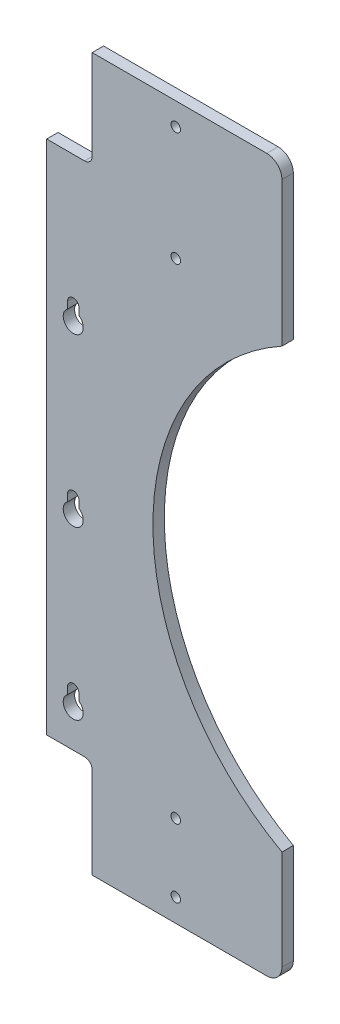
SolidWorks part; units mm, degrees
material "PC High Viscosity"
ref_plane "Front Plane" through (0, 0, 0) normal (0, 0, 1) x (1, 0, 0)
ref_plane "Top Plane" through (0, 0, 0) normal (0, 1, 0) x (1, 0, 0)
ref_plane "Right Plane" through (0, 0, 0) normal (1, 0, 0) x (0, 0, -1)
sketch "Sketch1" plane through (0, 0, 0) normal (0, 0, 1) x (1, 0, 0)
  line L0 (-174.625, 151.522) -> (-174.625, 311.15)
  line L1 (-174.625, -311.15) -> (174.625, -311.15)
  line L2 (-174.625, -311.15) -> (-174.625, -215.022)
  line L3 (-174.625, 311.15) -> (174.625, 311.15)
  line L4 (174.625, -311.15) -> (174.625, -215.022)
  line L5 (-174.625, -311.15) -> (174.625, 311.15) construction
  line L6 (-174.625, 311.15) -> (174.625, -311.15) construction
  line L7 (0, 311.15) -> (0, -311.15) construction
  line L8 (174.625, 151.522) -> (174.625, 311.15)
  line L10 (-316.9334, 298.842) -> (316.9334, 298.842) construction
  line L11 (-316.9334, 298.842) -> (-316.9334, 286.142) construction
  line L12 (-316.9334, 286.142) -> (316.9334, 286.142) construction
  line L13 (316.9334, 298.842) -> (316.9334, 286.142) construction
  arc A0 (-174.625, -215.022) -> (-174.625, 151.522) centre (-276.225, -31.75) ccw
  arc A1 (174.625, -215.022) -> (174.625, 151.522) centre (276.225, -31.75) cw
  point P0 (0, 0)
  point P14 (0, 249.0718)
  dimension "D3" = 419.1
  dimension "D1" = 622.3
  dimension "D2" = 349.25
  dimension "D4" = 279.4
  dimension "D5" = 101.6
  dimension "D6" = 12.7
  dimension "D7" = 134.62
extrude "Boss-Extrude1" add sketch "Sketch1" along normal blind 9.525
sketch "Sketch2" plane through (0, 0, 9.525) normal (0, 0, 1) x (1, 0, 0)
  line L0 (0, 311.15) -> (0, -311.15) construction
  line L1 (174.625, 311.15) -> (-174.625, 311.15) construction
  line L2 (-174.625, -311.15) -> (174.625, -311.15) construction
  line L3 (-66.675, -31.75) -> (66.675, -31.75) construction
  arc A0 (-174.625, -215.022) -> (-174.625, 151.522) centre (-276.225, -31.75) ccw construction
  arc A1 (174.625, 151.522) -> (174.625, -215.022) centre (276.225, -31.75) ccw construction
  point P6 (0, -191.262)
  point P7 (0, 88.138)
  point P16 (0, -51.562)
  dimension "D2" = 119.888
  dimension "D1" = 279.4
  dimension "D3" = 139.7
hole_wizard "V (0.377) Diameter Slot2" positions "Sketch3" profile "Sketch5" size "V" standard "ANSI Inch" slot yes end condition through all
sketch "Sketch3" plane through (0, 0, 9.525) normal (0, 0, 1) x (1, 0, 0)
  line L1 (0, -202.3745) -> (0, -180.1495) construction
  point P0 (0, -191.262)
  point P3 (0, 88.138)
  point P10 (0, -51.562)
  dimension "D1" = 22.225
sketch "Sketch5" plane through (0, -191.262, 9.525) normal (1, 0, 0) x (0, -1, 0)
  line L0 (0, 0) -> (0, 9.525)
  line L1 (0, 9.525) -> (4.7879, 9.525)
  line L2 (4.7879, 9.525) -> (4.7879, 0)
  line L5 (4.7879, 0) -> (0, 0)
  line L11 (0, -6.35) -> (0, 107.95) construction
  dimension "Thru Hole Dia." = 9.5758
  dimension "Thru Hole Depth" = 9.525
sketch "Sketch6" plane through (0, 0, 9.525) normal (0, 0, 1) x (1, 0, 0)
  line L0 (-174.625, -311.15) -> (174.625, -311.15) construction
  line L1 (-174.625, 311.15) -> (-22.225, 311.15)
  line L2 (-174.625, 311.15) -> (-174.625, -311.15)
  line L3 (-174.625, -311.15) -> (-22.225, -311.15)
  line L4 (-22.225, 311.15) -> (-22.225, -311.15)
  line L5 (174.625, 151.522) -> (174.625, 311.15) construction
  dimension "D1" = 196.85
extrude "Cut-Extrude1" cut sketch "Sketch6" against normal up to next
fillet "Fillet1" radius 12.7 1 edges at (174.625, -311.15, 4.7625)
sketch "Sketch7" plane through (0, 0, 9.525) normal (0, 0, 1) x (1, 0, 0)
  circle A0 centre (0, -197.5866) radius 8.382
  circle A1 centre (0, 81.8134) radius 8.382
  circle A2 centre (0, -57.8866) radius 8.382
  dimension "D1" = 16.764
extrude "Cut-Extrude2" cut sketch "Sketch7" against normal through all
sketch "Sketch9" plane through (0, 0, 9.525) normal (0, 0, 1) x (1, 0, 0)
  line L0 (137.2235, 251.5345) -> (137.2235, 184.8595) construction
  line L2 (174.625, 151.522) -> (174.625, 311.15) construction
  point P2 (137.2235, 218.197)
  dimension "D1" = 66.675
  dimension "D2" = 66.675
  dimension "D3" = 37.4015
sketch "Sketch12" plane through (0, 0, 9.525) normal (0, 0, 1) x (1, 0, 0)
  line L1 (-22.225, 311.15) -> (15.875, 311.15)
  line L2 (-22.225, 311.15) -> (-22.225, 203.2)
  line L3 (-22.225, 203.2) -> (15.875, 203.2)
  line L4 (15.875, 311.15) -> (15.875, 203.2)
  line L5 (-22.225, -311.15) -> (15.875, -311.15)
  line L6 (-22.225, -311.15) -> (-22.225, -228.6)
  line L7 (-22.225, -228.6) -> (15.875, -228.6)
  line L8 (15.875, -311.15) -> (15.875, -228.6)
  dimension "D1" = 38.1
  dimension "D2" = 107.95
  dimension "D3" = 82.55
extrude "Cut-Extrude3" cut sketch "Sketch12" against normal through all
fillet "Fillet2" radius 6.35 2 edges at (15.875, -228.6, 4.7625) (15.875, 203.2, 4.7625)
sketch "Sketch13" plane through (0, 0, 9.525) normal (0, 0, 1) x (1, 0, 0)
  line L0 (85.7885, 311.15) -> (85.7885, 55.6865) construction
  line L1 (174.625, 311.15) -> (15.875, 311.15) construction
  line L2 (174.625, 151.522) -> (174.625, 311.15) construction
  arc A0 (174.625, 151.522) -> (174.625, -215.022) centre (276.225, -31.75) ccw construction
  point P9 (85.7885, 265.938)
  point P10 (85.7885, 170.688)
  dimension "D1" = 88.8365
  dimension "D2" = 95.25
  dimension "D3" = 45.212
hole_wizard "5/16 (0.3125) Diameter Hole1" positions "Sketch14" profile "Sketch15" hole size "5/16" standard "ANSI Inch" end condition through all
sketch "Sketch14" plane through (0, 0, 9.525) normal (0, 0, 1) x (1, 0, 0)
  point P0 (85.7885, 170.688)
  point P5 (85.7885, 265.938)
sketch "Sketch15" plane through (85.7885, 170.688, 9.525) normal (1, 0, 0) x (0, -1, 0)
  line L0 (0, 0) -> (0, 9.525)
  line L1 (0, 9.525) -> (3.9687, 9.525)
  line L2 (3.9687, 9.525) -> (3.9687, 0)
  line L5 (3.9687, 0) -> (0, 0)
  line L11 (0, -6.35) -> (0, 107.95) construction
  dimension "Thru Hole Dia." = 7.9375
  dimension "Thru Hole Depth" = 9.525
sketch "Sketch16" plane through (0, 0, 9.525) normal (0, 0, 1) x (1, 0, 0)
  line L0 (174.625, 151.522) -> (174.625, 311.15) construction
  line L1 (15.875, 311.15) -> (174.625, 311.15)
  line L2 (15.875, 311.15) -> (15.875, 284.872)
  line L3 (15.875, 284.872) -> (174.625, 284.872)
  line L4 (174.625, 311.15) -> (174.625, 284.872)
  dimension "D1" = 133.35
extrude "Cut-Extrude4" cut sketch "Sketch16" against normal through all
sketch "Sketch17" plane through (0, 0, 9.525) normal (0, 0, 1) x (1, 0, 0)
  line L9 (174.625, 284.872) -> (15.875, 284.872)
  line L10 (15.875, 284.872) -> (15.875, 209.55)
  line L11 (9.525, 203.2) -> (-22.225, 203.2)
  line L12 (-22.225, 203.2) -> (-22.225, -228.6)
  line L13 (-22.225, -228.6) -> (9.525, -228.6)
  line L14 (15.875, -234.95) -> (15.875, -311.15)
  line L15 (15.875, -311.15) -> (161.925, -311.15)
  line L16 (174.625, -298.45) -> (174.625, -215.022)
  line L17 (174.625, 151.522) -> (174.625, 284.872)
  line L18 (174.625, 284.872) -> (15.875, 284.872)
  line L19 (15.875, 284.872) -> (15.875, 209.55)
  line L20 (9.525, 203.2) -> (-22.225, 203.2)
  line L21 (-22.225, 203.2) -> (-22.225, -228.6)
  line L22 (-22.225, -228.6) -> (9.525, -228.6)
  line L23 (15.875, -234.95) -> (15.875, -311.15)
  line L24 (15.875, -311.15) -> (161.925, -311.15)
  line L25 (174.625, -298.45) -> (174.625, -215.022)
  line L26 (174.625, 151.522) -> (174.625, 284.872)
  arc A4 (9.525, 203.2) -> (15.875, 209.55) centre (9.525, 209.55) ccw
  arc A5 (15.875, -234.95) -> (9.525, -228.6) centre (9.525, -234.95) ccw
  arc A6 (161.925, -311.15) -> (174.625, -298.45) centre (161.925, -298.45) ccw
  arc A7 (174.625, 151.522) -> (174.625, -215.022) centre (276.225, -31.75) ccw
  arc A8 (9.525, 203.2) -> (15.875, 209.55) centre (9.525, 209.55) ccw
  arc A9 (15.875, -234.95) -> (9.525, -228.6) centre (9.525, -234.95) ccw
  arc A10 (161.925, -311.15) -> (174.625, -298.45) centre (161.925, -298.45) ccw
  arc A11 (174.625, 151.522) -> (174.625, -215.022) centre (276.225, -31.75) ccw
  dimension "D1" = 0
sketch "Sketch18" plane through (0, 0, 9.525) normal (0, 0, 1) x (1, 0, 0)
  line L0 (174.625, -292.1) -> (15.875, -292.1) construction
  line L1 (174.625, -298.45) -> (174.625, -215.022) construction
  line L2 (15.875, -234.95) -> (15.875, -311.15) construction
  line L3 (15.875, -234.95) -> (174.625, -234.95) construction
  line L5 (85.7885, -292.1) -> (85.7885, -234.95) construction
  line L6 (85.7885, 311.15) -> (85.7885, 55.6865) construction
  line L7 (15.875, -311.15) -> (161.925, -311.15) construction
  point P8 (85.7885, -234.95)
  point P9 (85.7885, -292.1)
  dimension "D1" = 57.15
  dimension "D2" = 19.05
hole_wizard "5/16 (0.3125) Diameter Hole2" positions "Sketch19" profile "Sketch20" hole size "5/16" standard "ANSI Inch" end condition through all
sketch "Sketch19" plane through (0, 0, 9.525) normal (0, 0, 1) x (1, 0, 0)
  point P0 (85.7885, -234.95)
  point P3 (85.7885, -292.1)
sketch "Sketch20" plane through (85.7885, -234.95, 9.525) normal (1, 0, 0) x (0, -1, 0)
  line L0 (0, 0) -> (0, 9.525)
  line L1 (0, 9.525) -> (3.9687, 9.525)
  line L2 (3.9687, 9.525) -> (3.9687, 0)
  line L5 (3.9687, 0) -> (0, 0)
  line L11 (0, -6.35) -> (0, 107.95) construction
  dimension "Thru Hole Dia." = 7.9375
  dimension "Thru Hole Depth" = 9.525
sketch "Sketch21" plane through (0, 0, 9.525) normal (0, 0, 1) x (1, 0, 0)
  line L0 (-22.225, -228.6) -> (9.525, -228.6) construction
  line L1 (0, -183.6039) -> (0, 95.7961) construction
  line L2 (-22.225, 203.2) -> (-22.225, -228.6) construction
  circle A0 centre (0, 95.7961) radius 3.2639
  circle A1 centre (0, -183.6039) radius 3.2639
  circle A2 centre (0, -184.9374) radius 4.7879
  dimension "D3" = 6.5278
  dimension "D1" = 279.4
  dimension "D2" = 44.9961
  dimension "D4" = 22.225
fillet "Fillet3" radius 12.7 1 edges at (174.625, 284.872, 4.7625)
sketch "Sketch22" plane through (0, 0, 0) normal (0, 0, -1) x (-1, 0, 0)
  line L0 (3.175, 177.8) -> (28.575, 177.8) construction
  line L3 (22.225, 203.2) -> (-9.525, 203.2) construction
  line L4 (22.225, 203.2) -> (22.225, -228.6) construction
  text T0 "R" font "Century Gothic" height 12.7
  dimension "D1" = 25.4
  dimension "D2" = 25.4
  dimension "D3" = 19.05
extrude "Cut-Extrude5" cut sketch "Sketch22" against normal blind 1.27
equation "\"D3@Sketch9\"=1.3875+.17/2"
equation "\"D3@Sketch2\"=\"D1@Sketch2\"/2"
